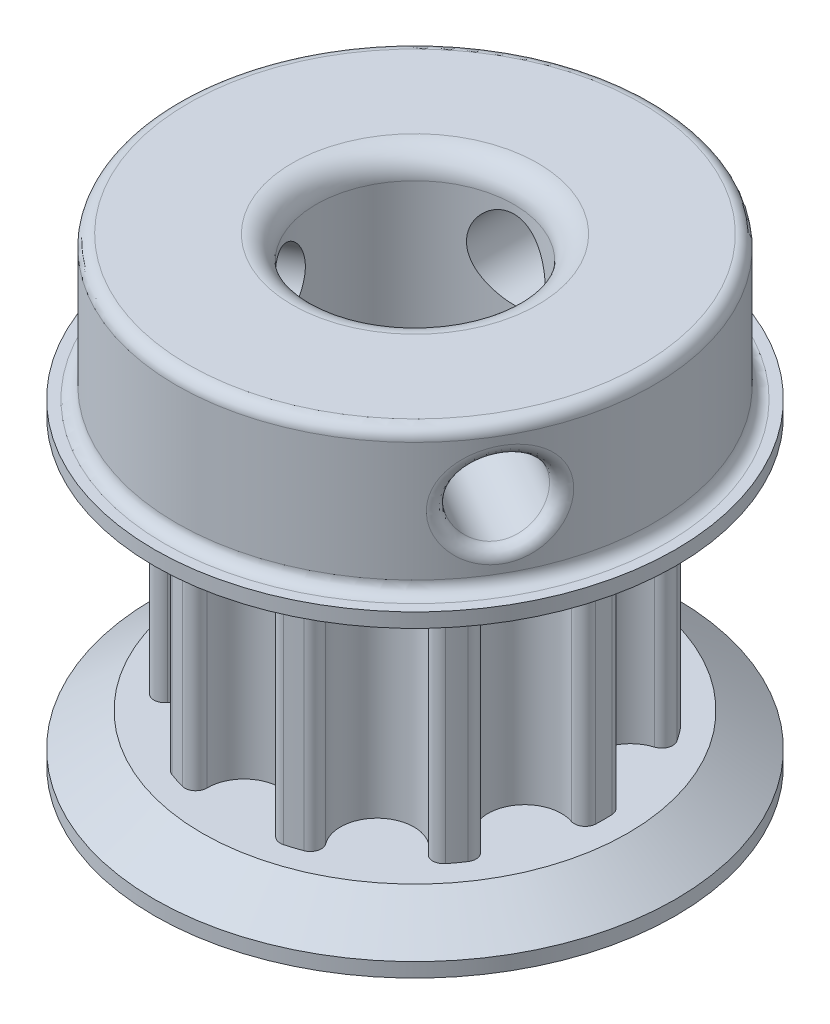
SolidWorks part; units mm, degrees
ref_plane "Plan de face" through (0, 0, 0) normal (0, 0, 1) x (1, 0, 0)
ref_plane "Plan de dessus" through (0, 0, 0) normal (0, 1, 0) x (1, 0, 0)
ref_plane "Plan de droite" through (0, 0, 0) normal (1, 0, 0) x (0, 0, -1)
sketch "Esquisse1" plane through (0, 0, 0) normal (0, 1, 0) x (1, 0, 0)
  line L0 (0, 0) -> (-2.449, 7.5372)
  line L2 (2.449, 7.5372) -> (0, 0)
  line L3 (0, 7.9251) -> (0, 0) construction
  line L4 (-2.449, 7.5372) -> (2.449, 7.5372) construction
  circle A1 centre (0, 0) radius 7.9251 construction
  arc A2 (-1.5429, 7.1881) -> (1.5429, 7.1881) centre (0, 7.1681) ccw
  arc A3 (-2.449, 7.5372) -> (-2.1236, 7.6353) centre (0, 0) cw
  arc A4 (-2.1236, 7.6353) -> (-1.5429, 7.1881) centre (-2.0008, 7.1941) cw
  arc A5 (2.449, 7.5372) -> (2.1236, 7.6353) centre (0, 0) ccw
  arc A6 (2.1236, 7.6353) -> (1.5429, 7.1881) centre (2.0008, 7.1941) ccw
  arc A7 (-1.5429, 7.1881) -> (-1.4081, 7.799) centre (0, 7.1681) cw construction
  arc A8 (1.5429, 7.1881) -> (1.4081, 7.799) centre (0, 7.1681) ccw construction
  point P6 (0, 5.6251)
  dimension "D2" = 1.543
  dimension "D3" = 0.458
  dimension "D1" = 4.898
  dimension "D4" = 2.3
  dimension "D5" = 36
extrude "Boss.-Extru.1" add sketch "Esquisse1" along normal blind 9.3
pattern_circular "Répétition circulaire1" count 10 over 360 about axis through (0, 9.3, 0) along (0, -1, 0) of "Boss.-Extru.1"
ref_plane "Plan1" through (0, 4.65, 0) normal (0, -1, 0) x (-1, 0, 0)
sketch "Esquisse2" plane through (0, 9.3, 0) normal (0, 1, 0) x (1, 0, 0)
  circle A0 centre (0, 0) radius 10.9251
  arc A1 (-6.2059, 4.9289) -> (-6.6054, 4.3791) centre (0, 0) ccw construction
  dimension "D1" = 3
extrude "Boss.-Extru.2" add sketch "Esquisse2" along normal blind 2
mirror "Symétrie1" about plane through (0, 4.65, 0) normal (0, -1, 0) of "Boss.-Extru.2"
chamfer "Chanfrein1" distance 2 angle 35 2 edges at (0, 9.3, 10.9251) (0, 0, 10.9251) first distance on face at (0, 9.3, 0) first distance on face at (0, 0, 0)
sketch "Esquisse4" plane through (0, 11.3, 0) normal (0, 1, 0) x (1, 0, 0)
  circle A0 centre (0, 0) radius 10
  dimension "D1" = 20
extrude "Boss.-Extru.3" add sketch "Esquisse4" along normal blind 6
sketch "Esquisse5" plane through (0, 0, 0) normal (0, 0, 1) x (1, 0, 0)
  line L0 (0, 0) -> (0, 14.3) construction
  line L1 (10, 17.3) -> (-10, 17.3) construction
  circle A0 centre (0, 14.3) radius 1.65
  dimension "D2" = 3.3
  dimension "D1" = 3
extrude "Enlèv. mat.-Extru.2" cut sketch "Esquisse5" against normal through all
pattern_circular "Répétition circulaire2" count 3 over 360 about axis through (0, 17.3, 0) along (0, -1, 0) of "Enlèv. mat.-Extru.2"
sketch "Esquisse3" plane through (0, 17.3, 0) normal (0, 1, 0) x (1, 0, 0)
  circle A0 centre (0, 0) radius 4.15
  dimension "D1" = 8.3
extrude "Enlèv. mat.-Extru.1" cut sketch "Esquisse3" against normal up to next
fillet "Congé1" radius 1 2 edges at (0, -2, -4.15) (0, 17.3, 4.15)
fillet "Congé2" radius 0.5 5 edges at (0, 11.3, 10) (0, 17.3, 10) (0.3544, 12.6885, -9.9937) (-7.7413, 13.9455, 6.3302) (9.3528, 13.9455, 3.5391)
equation "\"nb_tooth\"= 10"
equation "\"D5@Esquisse1\"=360/\"nb_tooth\""
equation "\"D1@Répétition circulaire1\"=\"nb_tooth\""
